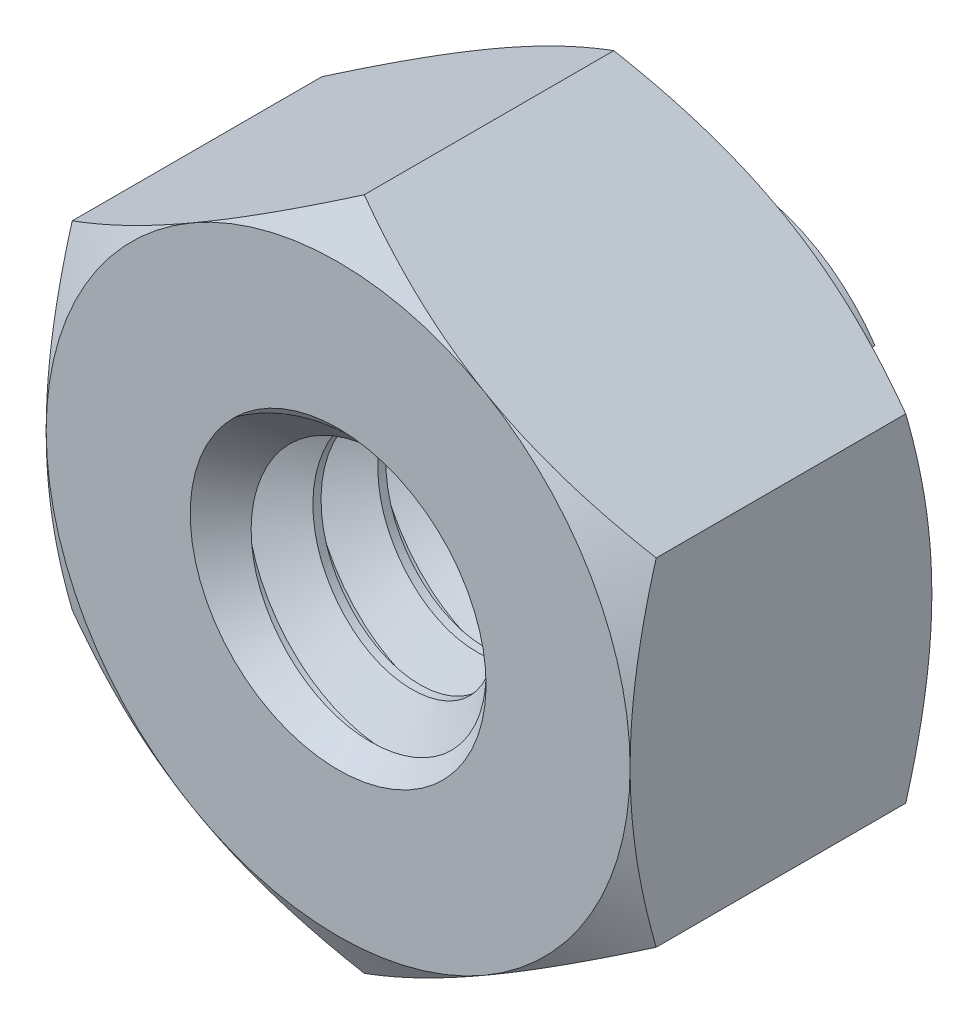
SolidWorks part; units mm, degrees
material "Cast Alloy Steel"
ref_plane "Front Plane" through (0, 0, 0) normal (0, 0, 1) x (1, 0, 0)
ref_plane "Top Plane" through (0, 0, 0) normal (0, 1, 0) x (1, 0, 0)
ref_plane "Right Plane" through (0, 0, 0) normal (1, 0, 0) x (0, 0, -1)
sketch "Sketch1" plane through (0, 0, 0) normal (0, 0, 1) x (1, 0, 0)
  line L1 (0, 5.4993) -> (-4.7625, 2.7496)
  line L2 (-4.7625, 2.7496) -> (-4.7625, -2.7496)
  line L3 (-4.7625, -2.7496) -> (0, -5.4993)
  line L4 (0, -5.4993) -> (4.7625, -2.7496)
  line L5 (4.7625, -2.7496) -> (4.7625, 2.7496)
  line L6 (4.7625, 2.7496) -> (0, 5.4993)
  circle A0 centre (0, 0) radius 4.7625 construction
  dimension "Hex" = 9.525
extrude "Extrude1" add sketch "Sketch1" against normal blind 6.35
sketch "Sketch2" plane through (0, 0, 0) normal (0, 0, 1) x (1, 0, 0)
  circle A0 centre (0, 0) radius 4.7625 construction
  circle A1 centre (0, 0) radius 4.7625
extrude "Cut-Extrude1" cut sketch "Sketch2" against normal through all draft 60 flip side to cut
sketch "Sketch4" plane through (0, 0, 0) normal (0, 0, 1) x (1, 0, 0)
  circle A0 centre (0, 0) radius 2.413
  dimension "Thread Dia" = 4.826
extrude "Cut-Extrude3" cut sketch "Sketch4" against normal through all
sketch "Sketch7" plane through (0, 0, 0) normal (0, 0, 1) x (1, 0, 0)
  circle A1 centre (0, 0) radius 2.413
  circle A2 centre (0, 0) radius 2.413
  dimension "D1" = 0
sketch "Sketch8" plane through (0, 0, -6.35) normal (0, 0, -1) x (-1, 0, 0)
  circle A1 centre (0, 0) radius 2.413
  circle A3 centre (0, 0) radius 2.413
  dimension "D1" = 0
sketch "Sketch5" plane through (0, 0, 0) normal (0, 0, 1) x (1, 0, 0)
  circle A0 centre (0, 0) radius 2.413 construction
  circle A1 centre (0, 0) radius 2.413
curve "Helix/Spiral1" pitch 1.0583 height 7.4083 turns 7 parameters "pitch"=1.0583
sketch "Sketch9" plane through (0, 0, 0) normal (1, 0, 0) x (0, 0, -1)
  line L0 (-0.5292, 1.7256) -> (-0.3969, 1.7256)
  line L1 (-0.3969, 1.7256) -> (0, 2.413)
  line L2 (-0.5292, 1.7256) -> (-0.926, 2.413)
  line L3 (-0.926, 2.413) -> (0, 2.413)
  line L4 (-0.463, 1.7256) -> (-0.463, 2.413) construction
  line L5 (-0.7276, 2.0693) -> (-0.1984, 2.0693) construction
  line L6 (0, 2.413) -> (0, -2.413) construction
  dimension "D1" = 0.1323
  dimension "D2" = 0.5292
  dimension "D3" = 60
sweep "Sweep1" add profiles "Sketch9" path "Helix/Spiral1"
sketch "Sketch10" plane through (0, 0, 0) normal (0, 0, 1) x (1, 0, 0)
  line L6 (0, 5.4993) -> (-4.7625, 2.7496)
  line L7 (-4.7625, 2.7496) -> (-4.7625, -2.7496)
  line L8 (-4.7625, -2.7496) -> (0, -5.4993)
  line L9 (0, -5.4993) -> (4.7625, -2.7496)
  line L10 (4.7625, -2.7496) -> (4.7625, 2.7496)
  line L11 (4.7625, 2.7496) -> (0, 5.4993)
  line L12 (0, 5.4993) -> (-4.7625, 2.7496)
  line L13 (-4.7625, 2.7496) -> (-4.7625, -2.7496)
  line L14 (-4.7625, -2.7496) -> (0, -5.4993)
  line L15 (0, -5.4993) -> (4.7625, -2.7496)
  line L16 (4.7625, -2.7496) -> (4.7625, 2.7496)
  line L17 (4.7625, 2.7496) -> (0, 5.4993)
  dimension "D1" = 0
extrude "Cut-Extrude8" cut sketch "Sketch10" along normal through all
sketch "Sketch11" plane through (0, 0, -6.35) normal (0, 0, -1) x (-1, 0, 0)
  line L6 (4.7625, 2.7496) -> (0, 5.4993)
  line L7 (4.7625, -2.7496) -> (4.7625, 2.7496)
  line L8 (0, -5.4993) -> (4.7625, -2.7496)
  line L9 (-4.7625, -2.7496) -> (0, -5.4993)
  line L10 (-4.7625, 2.7496) -> (-4.7625, -2.7496)
  line L11 (0, 5.4993) -> (-4.7625, 2.7496)
  line L12 (4.7625, 2.7496) -> (0, 5.4993)
  line L13 (4.7625, -2.7496) -> (4.7625, 2.7496)
  line L14 (0, -5.4993) -> (4.7625, -2.7496)
  line L15 (-4.7625, -2.7496) -> (0, -5.4993)
  line L16 (-4.7625, 2.7496) -> (-4.7625, -2.7496)
  line L17 (0, 5.4993) -> (-4.7625, 2.7496)
  dimension "D1" = 0
extrude "Cut-Extrude9" cut sketch "Sketch11" along normal through all
sketch "Sketch12" plane through (0, 0, -6.35) normal (0, 0, -1) x (-1, 0, 0)
  line L0 (0, 0) -> (4.7625, 2.7496) construction
  circle A0 centre (0, 0) radius 2.8956
  dimension "D1" = 5.7912
extrude "Cut-Extrude10" cut sketch "Sketch12" against normal blind 1.4287 flip side to cut
sketch "Sketch15" plane through (0, 0, -6.35) normal (0, 0, -1) x (-1, 0, 0)
  line L0 (0, 0) -> (0, -5.4993)
extrude "Cut-Extrude-Thin2" cut sketch "Sketch15" against normal offset from surface (0.9207 mm away) 0.508 thin up to face at (0, 0, -4.9213) thin type mid plane wall 0.381
pattern_circular "CirPattern1" count 6 over 360 about axis through (0, 0, 0) along (0, 0, 1) of "Cut-Extrude-Thin2"
sketch "Sketch3" plane through (0, 0, -4.9213) normal (0, 0, -1) x (-1, 0, 0)
  circle A1 centre (0, 0) radius 4.7625
  circle A2 centre (0, 0) radius 4.7625
  dimension "D1" = 0
extrude "Cut-Extrude2" cut sketch "Sketch3" against normal through all draft 60 flip side to cut
extrude "Cut-Extrude6" cut sketch "Sketch7" against normal through all draft 45
extrude "Cut-Extrude7" cut sketch "Sketch8" against normal through all draft 45
equation "\"D2@Sketch9\" = \"pitch@Helix/Spiral1\"*.5"
equation "\"D3@Helix/Spiral1\" = \"pitch@Helix/Spiral1\"+\"Height@Extrude1\""
equation "\"D1@Sketch9\" = \"pitch@Helix/Spiral1\"*.125"
equation "\"D1@Sketch12\" = \"Thread Dia@Sketch4\"*1.2"
equation "\"D1@Cut-Extrude10\" = \"Height@Extrude1\"*.225"
